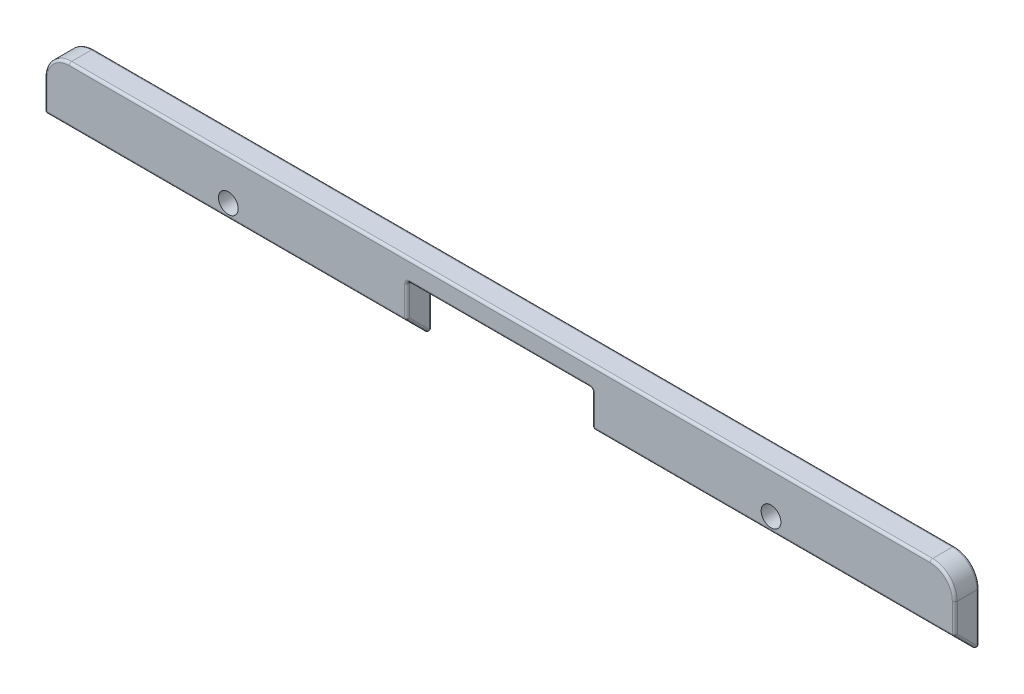
SolidWorks part; units mm, degrees
material "6061-T6 (SS)"
ref_plane "Front Plane" through (0, 0, 0) normal (0, 0, 1) x (1, 0, 0)
ref_plane "Top Plane" through (0, 0, 0) normal (0, 1, 0) x (1, 0, 0)
ref_plane "Right Plane" through (0, 0, 0) normal (1, 0, 0) x (0, 0, -1)
sketch "Sketch1" plane through (0, 0, 0) normal (1, 0, 0) x (0, 0, -1)
  line L0 (-3.0983, 0) -> (1.226, 0) construction
  line L1 (0, -3.2) -> (-2, -1.2)
  line L2 (0, -3.2) -> (0, 3.2)
  line L4 (-2, -1.2) -> (-2, 3.2)
  line L5 (-2, 3.2) -> (0, 3.2)
  dimension "D1" = 2
  dimension "D2" = 45
  dimension "D3" = 6.4
extrude "Boss-Extrude1" add sketch "Sketch1" along normal mid plane 73.8
fillet "Fillet1" radius 0.2 10 edges at (0, 3.2, 0) (0, 3.2, 2) (0, -3.2, 0) (0, -1.2, 2) (36.9, 1, 2) (36.9, 0, 0) (36.9, -2.2, 1) (-36.9, 1, 2) (-36.9, -2.2, 1) (-36.9, 0, 0)
sketch "Sketch4" plane through (0, 0, 0) normal (0, 0, 1) x (1, 0, 0)
  line L1 (7.5, 1.5) -> (-7.5, 1.5)
  line L2 (7.5, 1.5) -> (7.5, -3.2)
  line L3 (7.5, -3.2) -> (-7.5, -3.2)
  line L4 (-7.5, 1.5) -> (-7.5, -3.2)
  line L5 (0, 7.7759) -> (0, -8.8374) construction
  line L8 (-7.5, -3.2) -> (-7.5, 0.8) construction
  dimension "D1" = 4.7
hole_wizard "M2x0.4 Tapped Hole1" positions "Sketch2" profile "Sketch3" tap size "M2x0.4" standard "ANSI Metric" end condition through all
sketch "Sketch2" plane through (0, 0, 2) normal (0, 0, 1) x (1, 0, 0)
  circle A0 centre (-22, -0.2) radius 1.2
  circle A1 centre (-22, -0.2) radius 1.2 construction
  circle A2 centre (22, -0.2) radius 1.2
  circle A3 centre (22, -0.2) radius 1.2 construction
  point P0 (22, -0.2)
  point P2 (0, -0.2)
  point P5 (-22, -0.2)
sketch "Sketch3" plane through (22, -0.2, 2) normal (1, 0, 0) x (0, -1, 0)
  line L0 (0, 0) -> (0, 2)
  line L1 (0, 2) -> (0.8, 2)
  line L2 (0.8, 2) -> (0.8, 0)
  line L5 (0.8, 0) -> (0, 0)
  line L11 (0, -6.35) -> (0, 107.95) construction
  dimension "Thru Tap Drill Dia." = 1.6
  dimension "Thru Tap Drill Depth" = 2
cosmetic thread "Hole Thread1" parameters "D2"=2
cosmetic thread "Hole Thread2" parameters "D2"=2
cosmetic thread "Hole Thread3" parameters "D2"=2
extrude "Cut-Extrude4" cut sketch "Sketch4" along normal through all
fillet "Fillet2" radius 0.2 14 edges at (-7.5, -0.6086, 0) (-7.5, 0.1914, 2) (7.5, 0.1914, 2) (7.5, -0.6086, 0) (-7.5, -1.1937, 1.9848) (-7.5, -2.0586, 1.1414) (7.5, -1.1937, 1.9848) (7.5, -2.0586, 1.1414) (0, 1.5, 0) (0, 1.5, 2) (-7.5, 1.5, 1) (-7.5, -2.9019, 0.1235) (7.5, -2.9019, 0.1235) (7.5, 1.5, 1)
fillet "Fillet3" radius 2 6 edges at (36.8414, 3.1414, 1.9414) (36.8414, 3.1414, 0.0586) (-36.8414, 3.1414, 1.9414) (-36.8414, 3.1414, 0.0586) (-36.9, 3.2, 1) (36.9, 3.2, 1)
